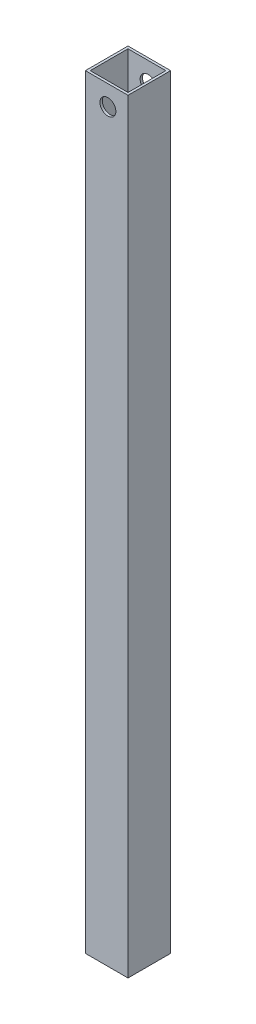
SolidWorks part; units mm, degrees
material "6061 Alloy"
ref_plane "Front Plane" through (0, 0, 0) normal (0, 0, 1) x (1, 0, 0)
ref_plane "Top Plane" through (0, 0, 0) normal (0, 1, 0) x (1, 0, 0)
ref_plane "Right Plane" through (0, 0, 0) normal (1, 0, 0) x (0, 0, -1)
sketch "Sketch1" plane through (0, 0, 0) normal (0, 1, 0) x (1, 0, 0)
  line L9 (12.7, -12.7) -> (-12.7, -12.7)
  line L10 (12.7, -12.7) -> (12.7, 12.7)
  line L11 (12.7, 12.7) -> (-12.7, 12.7)
  line L12 (-12.7, -12.7) -> (-12.7, 12.7)
  line L13 (12.7, -12.7) -> (-12.7, 12.7) construction
  line L14 (12.7, 12.7) -> (-12.7, -12.7) construction
  point P0 (0, 0)
  dimension "D1" = 25.4
extrude "Extrude-Thin1" add sketch "Sketch1" along normal blind 482.6 thin thin type mid plane wall 1.524
sketch "Sketch2" plane through (0, 0, 13.462) normal (0, 0, 1) x (1, 0, 0)
  line L0 (-13.462, 482.6) -> (13.462, 482.6) construction
  line L1 (13.462, 482.6) -> (13.462, 0) construction
  circle A0 centre (0.762, 469.9) radius 5.0419
  dimension "D1" = 10.0838
  dimension "D2" = 12.7
  dimension "D3" = 12.7
extrude "Cut-Extrude1" cut sketch "Sketch2" against normal through all
